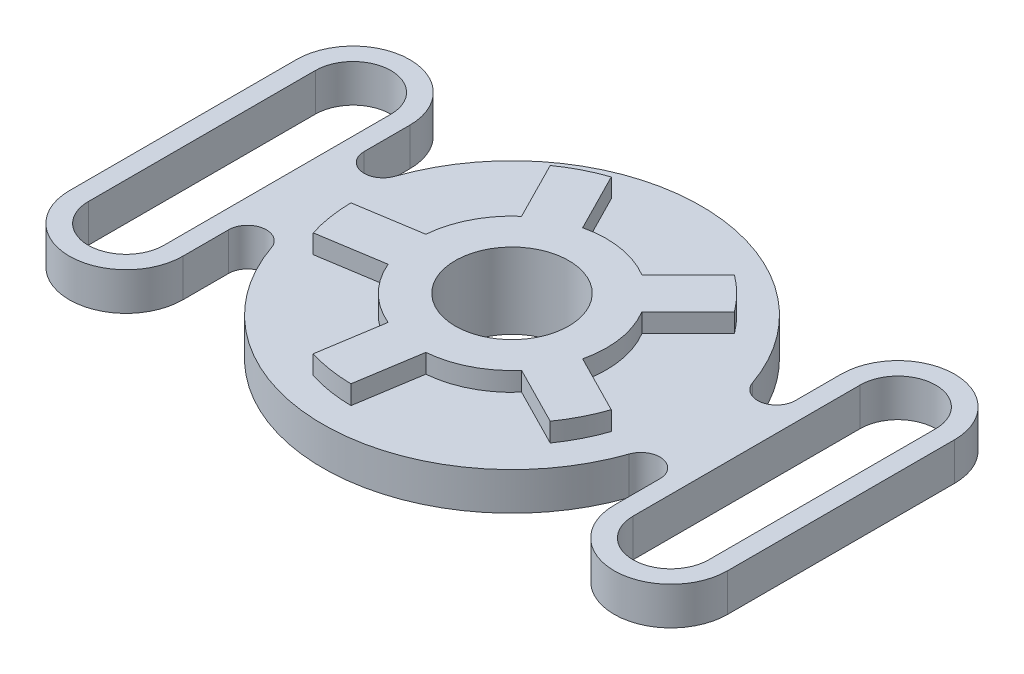
SolidWorks part; units mm, degrees
ref_plane "Front Plane" through (0, 0, 0) normal (0, 0, 1) x (1, 0, 0)
ref_plane "Top Plane" through (0, 0, 0) normal (0, 1, 0) x (1, 0, 0)
ref_plane "Right Plane" through (0, 0, 0) normal (1, 0, 0) x (0, 0, -1)
sketch "Sketch1" plane through (0, 0, 0) normal (0, 1, 0) x (1, 0, 0)
  line L0 (0, 0) -> (17041.7979, 0) construction
  line L1 (0, 0) -> (0, 17041.7979) construction
  line L2 (72, -30) -> (72, 30) construction
  line L3 (57, -30) -> (57, -17.9165)
  line L4 (87, -30) -> (87, 30)
  line L5 (72, 30) -> (72, -30) construction
  line L6 (82, 30) -> (82, -30)
  line L7 (62, 30) -> (62, -30)
  line L8 (-72, 30) -> (-72, -30) construction
  line L9 (-82, 30) -> (-82, -30)
  line L10 (-62, 30) -> (-62, -30)
  line L11 (-72, -30) -> (-72, 30) construction
  line L12 (-57, -30) -> (-57, -17.9165)
  line L13 (-87, -30) -> (-87, 30)
  line L14 (57, 17.9165) -> (57, 30)
  line L15 (-57, 17.9165) -> (-57, 30)
  line L16 (0, 0) -> (29.6985, 29.6985) construction
  line L17 (21.4036, 12.9184) -> (33.6365, 25.1512)
  line L18 (12.9184, 21.4036) -> (25.1512, 33.6365)
  line L19 (24.3481, -5.672) -> (39.7624, -13.526)
  line L20 (18.9002, -16.3641) -> (34.3145, -24.2181)
  line L21 (2.1296, -24.9091) -> (-0.5767, -41.996)
  line L22 (-9.7227, -23.0319) -> (-12.429, -40.1188)
  line L23 (-23.0319, -9.7227) -> (-40.1188, -12.429)
  line L24 (-24.9091, 2.1296) -> (-41.996, -0.5767)
  line L25 (-16.3641, 18.9002) -> (-24.2181, 34.3145)
  line L26 (-5.672, 24.3481) -> (-13.526, 39.7624)
  circle A0 centre (0, 0) radius 15
  circle A1 centre (0, 0) radius 25
  arc A2 (-13.526, 39.7624) -> (-24.2181, 34.3145) centre (0, 0) ccw
  arc A3 (47.2727, 16.2877) -> (-47.2727, 16.2877) centre (0, 0) ccw
  arc A4 (57, -30) -> (87, -30) centre (72, -30) ccw
  arc A5 (87, 30) -> (57, 30) centre (72, 30) ccw
  arc A6 (82, 30) -> (62, 30) centre (72, 30) ccw
  arc A7 (62, -30) -> (82, -30) centre (72, -30) ccw
  arc A8 (-82, 30) -> (-62, 30) centre (-72, 30) cw
  arc A9 (-62, -30) -> (-82, -30) centre (-72, -30) cw
  arc A10 (-57, -30) -> (-87, -30) centre (-72, -30) cw
  arc A11 (-87, 30) -> (-57, 30) centre (-72, 30) cw
  arc A12 (47.2727, 16.2877) -> (57, 17.9165) centre (52, 17.9165) ccw
  arc A13 (47.2727, -16.2877) -> (57, -17.9165) centre (52, -17.9165) cw
  arc A14 (-47.2727, -16.2877) -> (-57, -17.9165) centre (-52, -17.9165) ccw
  arc A15 (-47.2727, 16.2877) -> (-57, 17.9165) centre (-52, 17.9165) cw
  arc A16 (-47.2727, -16.2877) -> (47.2727, -16.2877) centre (0, 0) ccw
  arc A17 (-41.996, -0.5767) -> (-40.1188, -12.429) centre (0, 0) ccw
  arc A18 (-12.429, -40.1188) -> (-0.5767, -41.996) centre (0, 0) ccw
  arc A19 (34.3145, -24.2181) -> (39.7624, -13.526) centre (0, 0) ccw
  arc A20 (33.6365, 25.1512) -> (25.1512, 33.6365) centre (0, 0) ccw
  point P12 (72, 0)
  point P17 (72, 0)
  point P26 (-72, 0)
  point P33 (-72, 0)
  point P70 (-72, 0)
  point P72 (0, 0)
  dimension "D1" = 30
  dimension "D2" = 50
  dimension "D3" = 84
  dimension "D4" = 100
  dimension "D7" = 10
  dimension "D8" = 15
  dimension "D9" = 5
  dimension "D5" = 72
  dimension "D6" = 60
  dimension "D10" = 45
  dimension "D11" = 12
  dimension "D12" = 5
extrude "Boss-Extrude1" add sketch "Sketch1" along normal mid plane 20 contours A1 A0 | L26 A2 L25 A1 | L22 A18 L21 A1 | L24 A17 L23 A1 | L17 A20 L18 A1 | L20 A19 L19 A1 region at (23.5512, 0, -23.5512) region at (23.4029, 0, -6.5152) region at (29.6762, 0, 15.1208) region at (-15.1208, 0, -29.6762) region at (-5.2103, 0, 32.8963) region at (-32.8963, 0, 5.2103)
extrude "Boss-Extrude2" add sketch "Sketch1<3>" along normal mid plane 10 contours A14 A16 A13 L3 A4 L4 A5 L14 A12 A3 A15 L15 A11 L13 A10 L12 A20 L17 A1 L19 A19 L20 L21 A18 L22 L23 A17 L24 L25 A2 L26 L18 L10 A9 L9 A8 A7 L7 A6 L6 region at (59.0069, 0, 23.9582)
sketch "Sketch1<3>" plane through (0, 0, 0) normal (0, 1, 0) x (1, 0, 0) same geometry as "Sketch1"
